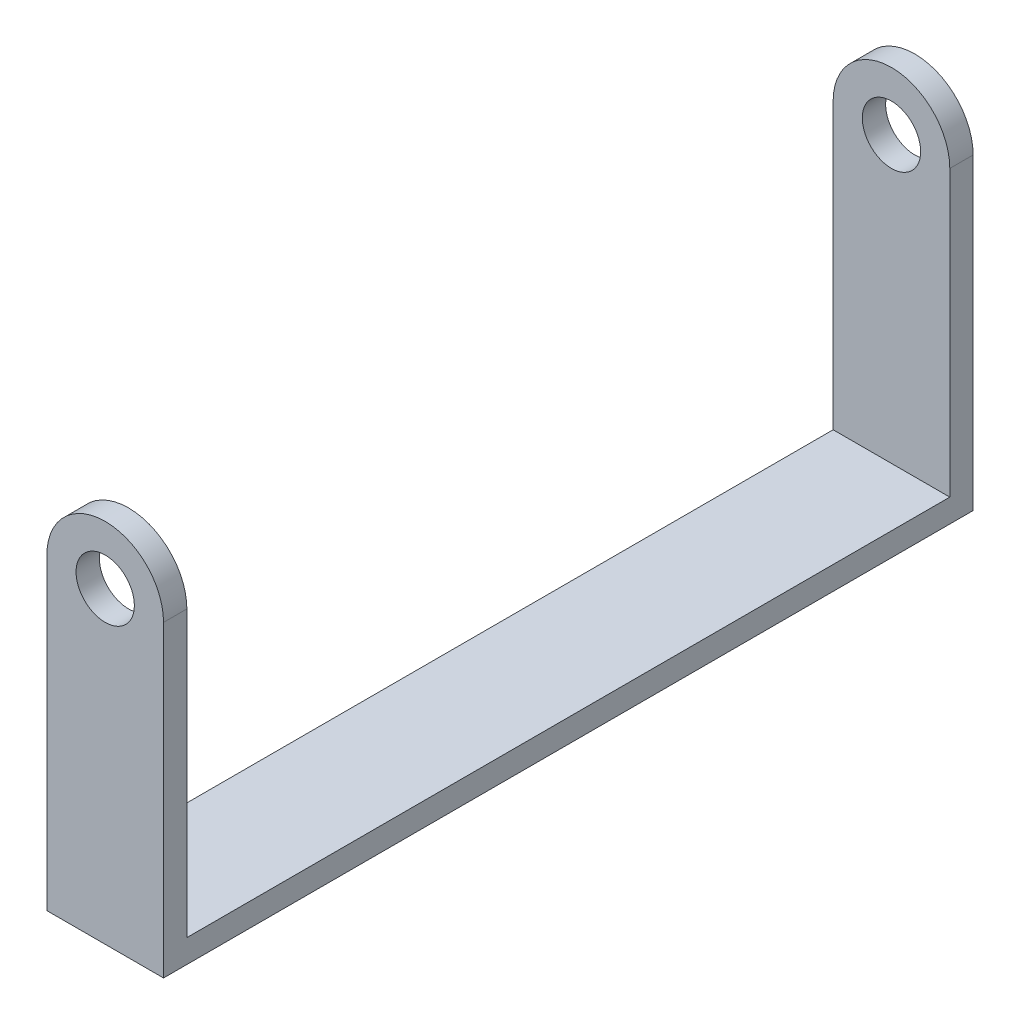
SolidWorks part; units mm, degrees
material "1060 Alloy"
ref_plane "Front Plane" through (0, 0, 0) normal (0, 0, 1) x (1, 0, 0)
ref_plane "Top Plane" through (0, 0, 0) normal (0, 1, 0) x (1, 0, 0)
ref_plane "Right Plane" through (0, 0, 0) normal (1, 0, 0) x (0, 0, -1)
sketch "Sketch1" plane through (0, 0, 0) normal (0, 0, 1) x (1, 0, 0)
  line L0 (0, 19.8538) -> (0, -21.8392) construction
  line L1 (-24.6755, 0) -> (26.59, 0) construction
  line L4 (-6.35, 0) -> (-6.35, -30.988)
  line L5 (-6.35, -30.988) -> (6.35, -30.988)
  line L6 (6.35, 0) -> (6.35, -30.988)
  line L7 (-1.2747, 6.2207) -> (6.35, -30.988) construction
  line L8 (-6.35, -30.988) -> (1.2747, 6.2207) construction
  circle A0 centre (0, 0) radius 3.175
  arc A1 (6.35, 0) -> (-6.35, 0) centre (0, 0) ccw
  point P12 (-6.35, 0)
  dimension "D1" = 6.35
  dimension "D2" = 12.7
  dimension "D3" = 30.988
extrude "Boss-Extrude1" add sketch "Sketch1" along normal blind 2.54
sketch "Sketch2" plane through (0, 0, 2.54) normal (0, 0, 1) x (1, 0, 0)
  line L0 (0, 12.118) -> (0, -18.5266) construction
sketch "Sketch3" plane through (0, -30.988, 0) normal (0, -1, 0) x (1, 0, 0)
  line L0 (-6.35, 2.54) -> (6.35, 2.54) construction
  line L1 (-6.35, 0) -> (6.35, 0)
  line L2 (-6.35, 0) -> (-6.35, 44.069)
  line L3 (-6.35, 44.069) -> (6.35, 44.069)
  line L4 (6.35, 0) -> (6.35, 44.069)
  point P5 (6.35, 0)
  dimension "D1" = 41.529
extrude "Boss-Extrude2" add sketch "Sketch3" along normal blind 2.54
mirror "Mirror3" about plane through (-6.35, -33.528, 44.069) normal (0, 0, -1) of bodies 102
